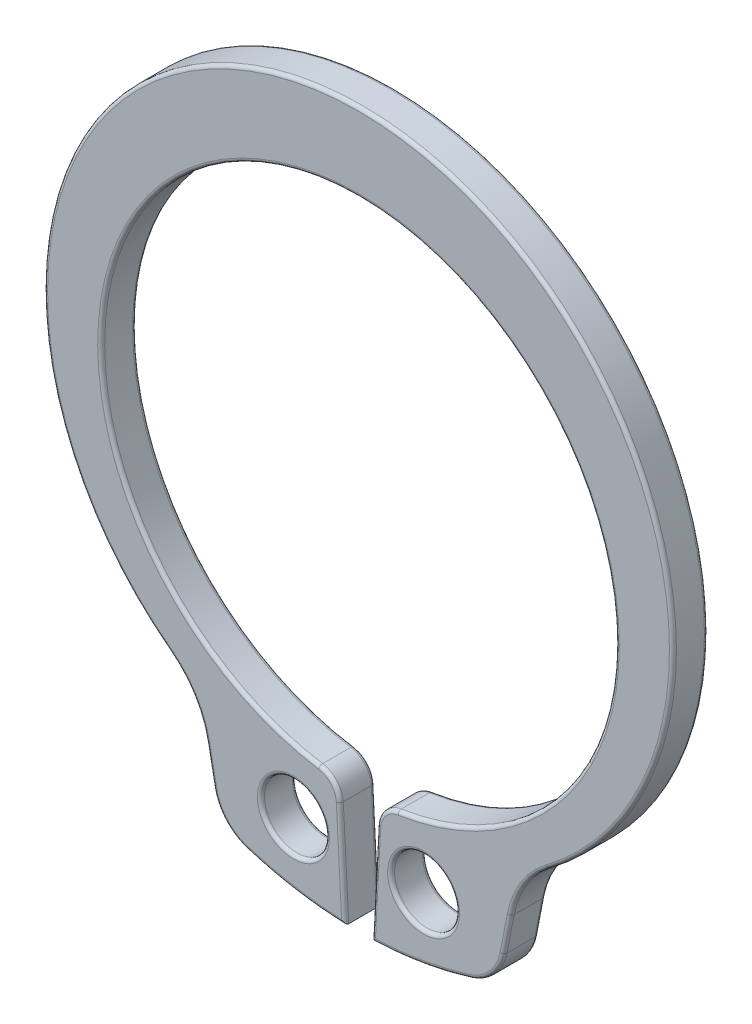
SolidWorks part; units mm, degrees
ref_plane "Front" through (0, 0, 0) normal (0, 0, 1) x (1, 0, 0)
ref_plane "Top" through (0, 0, 0) normal (0, 1, 0) x (1, 0, 0)
ref_plane "Right" through (0, 0, 0) normal (1, 0, 0) x (0, 0, -1)
sketch "Sketch1" plane through (0, 0, 0) normal (0, 0, 1) x (1, 0, 0)
  line L0 (0, 0) -> (-6.3653, -3.675) construction
  line L1 (0, 10.855) -> (0, -10.855) construction
  line L2 (-3.9914, -10.1017) -> (-4.5673, -7.1301) construction
  line L4 (-4.5673, -7.1301) -> (-5.1701, -8.0711) construction
  line L5 (-4.5673, -7.1301) -> (0, 0) construction
  line L6 (0, 7.35) -> (0, 9.585) construction
  line L7 (0, 9.585) -> (0, 8.4675) construction
  line L8 (0, -7.35) -> (0, -10.855) construction
  line L9 (-2.2174, -10.6329) -> (0, 0) construction
  line L10 (0, 0) -> (-0.3791, -10.855) construction
  line L11 (-3.9914, -10.1017) -> (0, 0) construction
  line L12 (-4.3762, -8.1161) -> (-5.4022, -6.5718) construction
  line L13 (-4.8892, -7.3439) -> (-4.5673, -7.1301) construction
  line L14 (-1.5005, -7.1952) -> (-2.2174, -10.6329) construction
  line L15 (-1.859, -8.914) -> (-0.9515, -9.1033) construction
  arc A0 (0, 9.585) -> (-4.5673, -7.1301) centre (0, 0.6035) ccw construction
  circle A2 centre (0, 0) radius 9.585 construction
  arc A3 (-3.9914, -10.1017) -> (-0.3791, -10.855) centre (0, 0) ccw construction
  circle A4 centre (0, 0) radius 7.35 construction
  circle A6 centre (-1.859, -8.914) radius 0.927 construction
  arc A7 (-5.4022, -6.5718) -> (-4.3762, -8.1161) centre (-7.0787, -8.7986) cw construction
  point P5 (-6.3653, -3.675)
  point P24 (-3.5222, -8.9144)
  point P35 (0, 9.585)
  point P36 (0, 7.35)
  point P37 (0, -7.35)
  point P38 (0, -10.855)
  dimension "Ring ID" = 14.7
  dimension "Hole Diameter" = 1.854
  dimension "D10" = 2.7874
  dimension "Max Sec." = 2.235
  dimension "Lug Height" = 3.505
  dimension "D6" = 2
  dimension "D5" = 3.0269
  dimension "D8" = 1.854
  dimension "D3" = 120
  dimension "D2" = 3.708
  dimension "D4" = 1.854
sketch "Sketch5" plane through (0, 0, 0) normal (0, 1, 0) x (1, 0, 0)
  line L0 (-9.585, 0.5) -> (-9.585, -0.5) construction
  line L2 (0, 0.5) -> (0, -0.5) construction
  line L4 (-9.585, 0) -> (9.585, 0) construction
  point P3 (-9.585, 0)
  point P6 (0, 0)
  dimension "Ring Thickness" = 1
sketch "Sketch2" plane through (0, 0, 0) normal (0, 0, 1) x (1, 0, 0)
  line L0 (-3.9914, -10.1017) -> (-4.5673, -7.1301) construction
  line L1 (-3.9914, -10.1017) -> (-4.5673, -7.1301)
  line L2 (0, 9.585) -> (0, 7.35)
  line L3 (0, 0) -> (-0.3791, -10.855) construction
  line L5 (-0.3791, -10.855) -> (-0.5639, -7.3283)
  arc A0 (0, 9.585) -> (-4.5673, -7.1301) centre (0, 0.6035) ccw construction
  arc A1 (-3.9914, -10.1017) -> (-0.3791, -10.855) centre (0, 0) ccw construction
  circle A2 centre (-1.859, -8.914) radius 0.927 construction
  arc A4 (0, 9.585) -> (-4.5673, -7.1301) centre (0, 0.6035) ccw
  arc A5 (-3.9914, -10.1017) -> (-0.3791, -10.855) centre (0, 0) ccw
  circle A6 centre (-1.859, -8.914) radius 0.927
  circle A7 centre (0, 0) radius 7.35 construction
  arc A8 (0, 7.35) -> (-0.5639, -7.3283) centre (0, 0) ccw
  dimension "D1" = 5
extrude "Boss-Extrude1" add sketch "Sketch2" along normal mid plane 1
fillet "Fillet1" radius 2.7874 1 edges at (-4.5673, -7.1301, 0)
fillet "Fillet2" radius 1.3937 1 edges at (-3.9914, -10.1017, 0)
fillet "Fillet3" radius 0.6968 1 edges at (-0.5639, -7.3283, 0)
mirror "Mirror1" about plane through (0, 9.585, 0.5) normal (-1, 0, 0) of bodies 109
sketch "Sketch3" plane through (0, 0, 0.5) normal (0, 0, 1) x (1, 0, 0)
  line L0 (4.7088, -5.6436) -> (5.4062, -6.5688) construction
  line L1 (5.4062, -6.5688) -> (6.3314, -5.8714) construction
  line L2 (0, 9.585) -> (0, 7.35) construction
  circle A0 centre (0, 0) radius 7.35 construction
  arc A1 (5.4062, -6.5688) -> (-5.4062, -6.5688) centre (0, 0.6035) ccw construction
fillet "Fillet4" radius 0.1 32 edges at (4.7196, -7.3184, -0.5) (4.2454, -8.7908, -0.5) (3.8115, -9.984, -0.5) (1.7968, -10.712, -0.5) (0, 7.35, -0.5) (-1.7968, -10.712, -0.5) (-3.8115, -9.984, -0.5) (-4.2454, -8.7908, -0.5) (-4.7196, -7.3184, -0.5) (4.7196, -7.3184, 0.5) (4.2454, -8.7908, 0.5) (3.8115, -9.984, 0.5) (1.7968, -10.712, 0.5) (0, 7.35, 0.5) (-1.7968, -10.712, 0.5) (-3.8115, -9.984, 0.5) (-4.2454, -8.7908, 0.5) (-4.7196, -7.3184, 0.5) (0, 9.585, -0.5) (0, 9.585, 0.5) (0.4561, -9.3855, -0.5) (0.712, -7.4852, -0.5) (-0.712, -7.4852, -0.5) (-0.4561, -9.3855, -0.5) (0.4561, -9.3855, 0.5) (0.712, -7.4852, 0.5) (-0.712, -7.4852, 0.5) (-0.4561, -9.3855, 0.5) (0.932, -8.914, -0.5) (-0.932, -8.914, -0.5) (0.932, -8.914, 0.5) (-0.932, -8.914, 0.5)
equation "\"D1@Fillet1\" = \"D10@Sketch1\""
equation "\"D1@Fillet2\"=\"D10@Sketch1\" / 2"
equation "\"Thickness@Boss-Extrude1\"=\"Ring Thickness@Sketch5\""
equation "\"D2@Sketch1\"=\"Hole Diameter@Sketch1\"*2"
equation "\"D4@Sketch1\"=\"D2@Sketch1\"/2"
equation "\"D8@Sketch1\"=\"D4@Sketch1\""
equation "\"D1@Fillet3\"=\"D1@Fillet2\"*.5"
equation "\"D1@Fillet4\"=\"Ring Thickness@Sketch5\"*.1"
